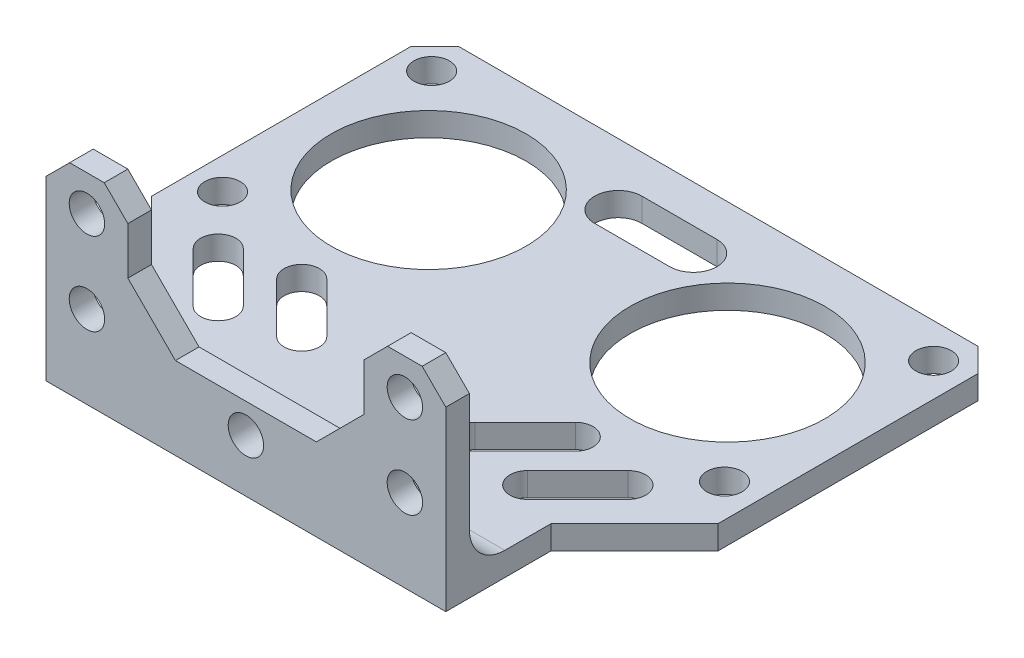
SolidWorks part; units mm, degrees
ref_plane "Front" through (0, 0, 0) normal (0, 0, 1) x (1, 0, 0)
ref_plane "Top" through (0, 0, 0) normal (0, 1, 0) x (1, 0, 0)
ref_plane "Right" through (0, 0, 0) normal (1, 0, 0) x (0, 0, -1)
sketch "Sketch1" plane through (0, 0, 0) normal (0, 1, 0) x (1, 0, 0)
  line L0 (-24, -12) -> (-16.9289, -19.0711)
  line L2 (-24, -12) -> (-24, 12)
  line L3 (-24, 12) -> (24, 12)
  line L4 (24, -12) -> (24, 12)
  line L5 (-24, -12) -> (24, 12) construction
  line L6 (-24, 12) -> (24, -12) construction
  line L7 (0, -12) -> (0, -28) construction
  line L8 (-16.9289, -19.0711) -> (-16.9289, -28)
  line L9 (-16.9289, -28) -> (16.9289, -28)
  line L10 (16.9289, -19.0711) -> (16.9289, -28)
  line L11 (24, -12) -> (16.9289, -19.0711)
  point P0 (0, 0)
  dimension "D1" = 48
  dimension "D2" = 24
  dimension "D4" = 10
  dimension "D5" = 16
extrude "Boss-Extrude1" add sketch "Sketch1" along normal blind 2
sketch "Sketch2" plane through (0, 2, 0) normal (0, 1, 0) x (1, 0, 0)
  line L0 (16.9289, -28) -> (16.9289, -19.0711) construction
  line L1 (-16.9289, -28) -> (16.9289, -28)
  line L2 (-16.9289, -28) -> (-16.9289, -26)
  line L3 (-16.9289, -26) -> (16.9289, -26)
  line L4 (16.9289, -28) -> (16.9289, -26)
  dimension "D1" = 2
extrude "Boss-Extrude2" add sketch "Sketch2" along normal blind 15
sketch "Sketch4" plane through (0, 2, 0) normal (0, 1, 0) x (1, 0, 0)
  circle A0 centre (-21.3236, -8.6566) radius 1.5
  circle A1 centre (-21.3236, 9.0534) radius 1.5
  circle A2 centre (21.1864, 9.0534) radius 1.5
  circle A3 centre (21.1864, -8.6566) radius 1.5
  dimension "D1" = 3
extrude "Cut-Extrude5" cut sketch "Sketch4" against normal blind 10
sketch "Sketch5" plane through (0, 0, 0) normal (0, -1, 0) x (-1, 0, 0)
  line L0 (-3.1114, 8.7834) -> (3.2486, 8.7834)
  line L1 (-3.1114, 4.7834) -> (3.2486, 4.7834)
  circle A0 centre (-12.5864, 0.1984) radius 8.25
  circle A1 centre (12.7236, 0.1984) radius 8.25
  arc A2 (-3.1114, 8.7834) -> (-3.1114, 4.7834) centre (-3.1114, 6.7834) ccw
  arc A3 (3.2486, 4.7834) -> (3.2486, 8.7834) centre (3.2486, 6.7834) ccw
  dimension "D1" = 16.5
extrude "Cut-Extrude6" cut sketch "Sketch5" against normal blind 10
sketch "Sketch6" plane through (0, 0, 0) normal (0, -1, 0) x (-1, 0, 0)
  line L0 (-17.347, -12.9962) -> (-13.1043, -17.2388) construction
  line L5 (-16.2863, -11.9355) -> (-12.0437, -16.1782)
  line L6 (-18.4076, -14.0569) -> (-14.165, -18.2995)
  line L7 (-11.5835, -11.6885) -> (-7.3409, -15.9312) construction
  line L8 (-10.5229, -10.6279) -> (-6.2802, -14.8705)
  line L9 (-12.6442, -12.7492) -> (-8.4016, -16.9918)
  line L10 (-16.9289, -19.0711) -> (-24, -12) construction
  line L11 (0, -28) -> (0, 12) construction
  line L12 (16.9289, -28) -> (-16.9289, -28) construction
  line L13 (-24, 12) -> (24, 12) construction
  line L14 (11.5835, -11.6885) -> (7.3409, -15.9312) construction
  line L15 (10.5229, -10.6279) -> (6.2802, -14.8705)
  line L16 (12.6442, -12.7492) -> (8.4016, -16.9918)
  line L17 (17.347, -12.9962) -> (13.1043, -17.2388) construction
  line L18 (16.2863, -11.9355) -> (12.0437, -16.1782)
  line L19 (18.4076, -14.0569) -> (14.165, -18.2995)
  line L20 (-11, -23.1923) -> (11, -23.1923) construction
  line L21 (-11, -21.1923) -> (11, -21.1923)
  line L22 (-11, -25.1923) -> (11, -25.1923)
  arc A2 (-16.2863, -11.9355) -> (-18.4076, -14.0569) centre (-17.347, -12.9962) ccw
  arc A3 (-14.165, -18.2995) -> (-12.0437, -16.1782) centre (-13.1043, -17.2388) ccw
  arc A4 (-10.5229, -10.6279) -> (-12.6442, -12.7492) centre (-11.5835, -11.6885) ccw
  arc A5 (-8.4016, -16.9918) -> (-6.2802, -14.8705) centre (-7.3409, -15.9312) ccw
  arc A6 (10.5229, -10.6279) -> (12.6442, -12.7492) centre (11.5835, -11.6885) cw
  arc A7 (8.4016, -16.9918) -> (6.2802, -14.8705) centre (7.3409, -15.9312) cw
  arc A8 (16.2863, -11.9355) -> (18.4076, -14.0569) centre (17.347, -12.9962) cw
  arc A9 (14.165, -18.2995) -> (12.0437, -16.1782) centre (13.1043, -17.2388) cw
  arc A10 (-11, -21.1923) -> (-11, -25.1923) centre (-11, -23.1923) ccw
  arc A11 (11, -25.1923) -> (11, -21.1923) centre (11, -23.1923) ccw
  point P2 (-15.2256, -15.1175)
  point P7 (-9.4622, -13.8099)
  point P24 (9.4622, -13.8099)
  point P31 (15.2256, -15.1175)
  point P38 (0, -23.1923)
  dimension "D1" = 3
  dimension "D2" = 6
  dimension "D3" = 2
  dimension "D4" = 4
  dimension "D5" = 4
  dimension "D6" = 22
extrude "Cut-Extrude7" cut sketch "Sketch6" against normal through all
sketch "Sketch7" plane through (0, 0, 26) normal (0, 0, -1) x (-1, 0, 0)
  line L0 (16.9289, 17) -> (9.997, 17)
  line L1 (-16.9289, 17) -> (16.9289, 17) construction
  line L2 (9.997, 17) -> (9.997, 11)
  line L3 (9.997, 11) -> (5.9676, 6.9706)
  line L4 (0, 17) -> (0, 5.7697) construction
  line L5 (5.9676, 6.9706) -> (-5.9676, 6.9706)
  line L6 (-9.997, 17) -> (-9.997, 11)
  line L7 (-9.997, 11) -> (-5.9676, 6.9706)
  line L8 (9.997, 17) -> (-9.997, 17)
  line L9 (13.463, 17) -> (13.463, 7.7079) construction
  circle A0 centre (13.463, 14) radius 1.5
  circle A1 centre (13.463, 7) radius 1.5
  circle A2 centre (-13.463, 14) radius 1.5
  circle A3 centre (-13.463, 7) radius 1.5
  circle A4 centre (0, 4.4706) radius 1.5
  point P14 (0, 6.9706)
  line M13 (16.9289, 17) -> (-16.9289, 17)
  dimension "D2" = 3
  dimension "D5" = 2.5
  dimension "D1" = 6
  dimension "D3" = 3
  dimension "D4" = 7
extrude "Cut-Extrude8" cut sketch "Sketch7" against normal through all contours L6 L7 L5 L3 L2 M13 | A4 | A3 | A2 | A1 | A0 region at (0, 12.3088, 26) region at (-13.463, 14, 26) region at (-13.463, 7, 26) region at (13.463, 14, 26) region at (13.463, 7, 26) region at (0, 4.4706, 26)
fillet "Fillet1" radius 3 1 edges at (0, 2, 26)
chamfer "Chamfer1" distance 2 angle 45 6 edges at (-16.9289, 17, 27) (16.9289, 17, 27) (-24, 1, -12) (24, 1, -12) (9.997, 17, 27) (-9.997, 17, 27)
